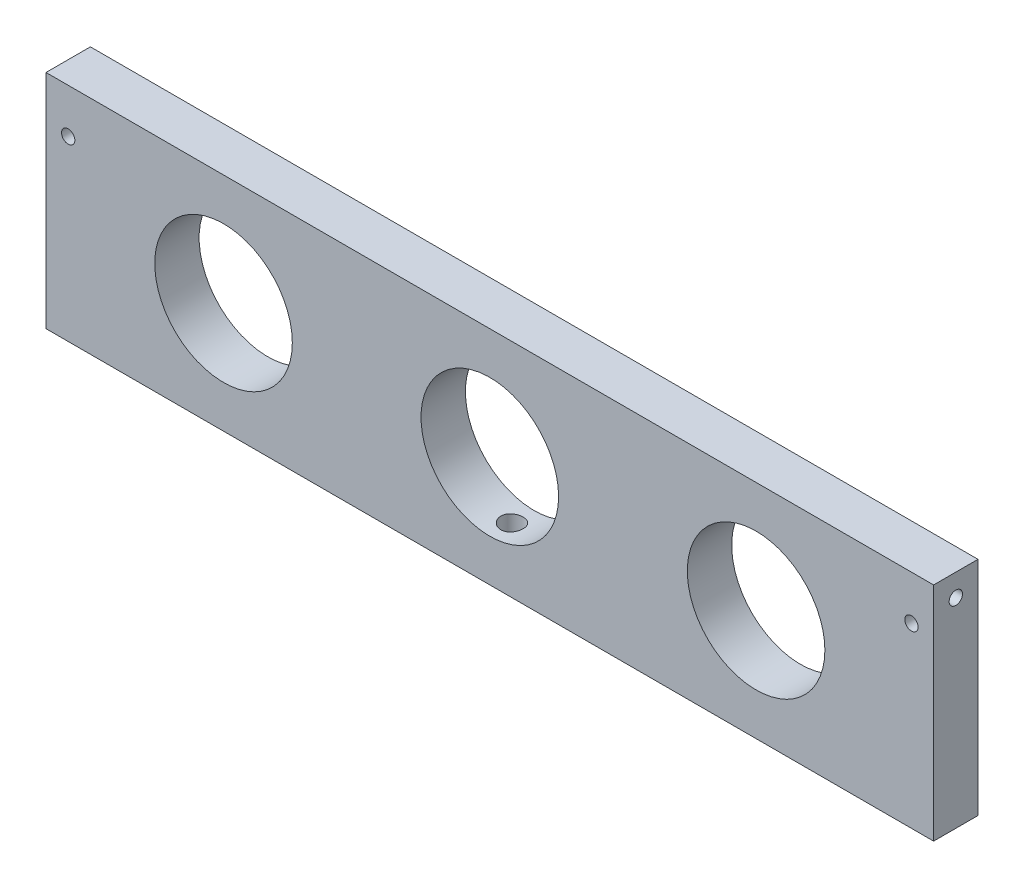
SolidWorks part; units mm, degrees
material "Perspex (TM) GS Acrylic Cast Sheet"
ref_plane "Front Plane" through (0, 0, 0) normal (0, 0, 1) x (1, 0, 0)
ref_plane "Top Plane" through (0, 0, 0) normal (0, 1, 0) x (1, 0, 0)
ref_plane "Right Plane" through (0, 0, 0) normal (1, 0, 0) x (0, 0, -1)
sketch "Sketch1" plane through (0, 0, 0) normal (0, 0, 1) x (1, 0, 0)
  line L1 (-100, 25) -> (100, 25)
  line L2 (-100, 25) -> (-100, -25)
  line L3 (-100, -25) -> (100, -25)
  line L4 (100, 25) -> (100, -25)
  line L5 (-100, 25) -> (100, -25) construction
  line L6 (-100, -25) -> (100, 25) construction
  circle A0 centre (0, 0) radius 15.5
  circle A1 centre (60, 0) radius 15.5
  circle A2 centre (-60, 0) radius 15.5
  circle A3 centre (95, 15) radius 1.5
  circle A4 centre (-95, 15) radius 1.5
  point P0 (0, 0)
  dimension "D3" = 31
  dimension "D4" = 60
  dimension "D5" = 60
  dimension "D6" = 3
  dimension "D7" = 10
  dimension "D8" = 5
  dimension "D9" = 5
  dimension "D1" = 200
  dimension "D2" = 50
extrude "Boss-Extrude1" add sketch "Sketch1" along normal blind 10
sketch "Sketch2" plane through (0, -25, 0) normal (0, -1, 0) x (1, 0, 0)
  line L0 (-100, 10) -> (100, 10) construction
  line L1 (-100, 10) -> (-100, 0) construction
  line L2 (100, 10) -> (100, 0) construction
  circle A0 centre (-95, 5) radius 2.5
  circle A1 centre (0, 5) radius 2.5
  circle A2 centre (95, 5) radius 2.5
  dimension "D1" = 5
  dimension "D2" = 5
  dimension "D3" = 5
  dimension "D4" = 5
extrude "Cut-Extrude1" cut sketch "Sketch2" against normal blind 10
sketch "Sketch3" plane through (100, 0, 0) normal (1, 0, 0) x (0, 0, -1)
  line L0 (0, -25) -> (0, 25) construction
  line L1 (-10, 25) -> (0, 25) construction
  circle A0 centre (-5, 20) radius 1.5
  dimension "D1" = 3
  dimension "D2" = 5
  dimension "D3" = 5
extrude "Cut-Extrude2" cut sketch "Sketch3" against normal blind 200
